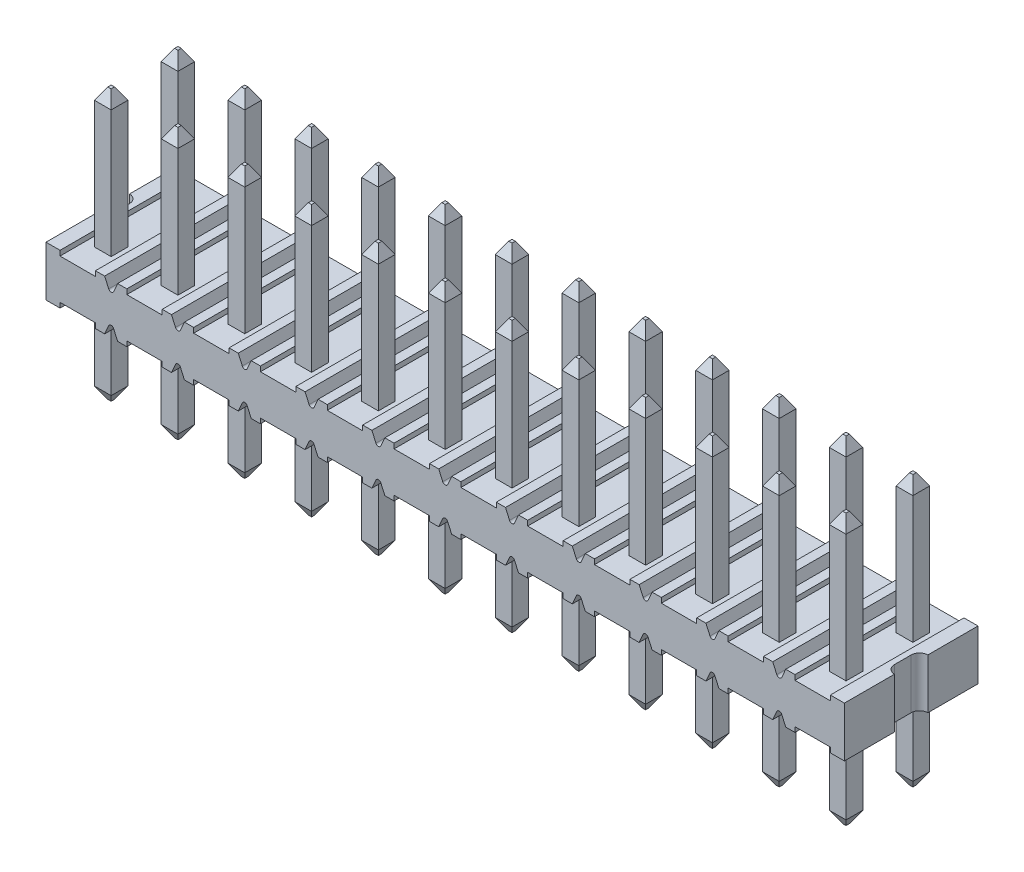
SolidWorks part; units mm, degrees
ref_plane "Front Plane" through (0, 0, 0) normal (0, 0, 1) x (1, 0, 0)
ref_plane "Top Plane" through (0, 0, 0) normal (0, 1, 0) x (1, 0, 0)
ref_plane "Right Plane" through (0, 0, 0) normal (1, 0, 0) x (0, 0, -1)
ref_plane "Plane1" through (0, -0.75, 0) normal (0, -1, 0) x (1, 0, 0)
sketch "Sketch1" plane through (0, -0.75, 0) normal (0, -1, 0) x (1, 0, 0)
  line L0 (-11.95, -2) -> (11.95, -2)
  line L1 (11.95, -2) -> (11.95, 2)
  line L2 (11.95, 2) -> (-11.95, 2)
  line L3 (-11.95, 2) -> (-11.95, -2)
extrude "Boss-Extrude1" add sketch "Sketch1" against normal blind 1.5
sketch "Sketch2" plane through (0, 0, -2) normal (0, 0, -1) x (-1, 0, 0)
  line L0 (-10.1944, 0.75) -> (-10.0731, 0.4775)
  line L1 (-9.9269, 0.4775) -> (-9.8056, 0.75)
  line L2 (-9.8056, 0.75) -> (-10.1944, 0.75)
  arc A0 (-10.0731, 0.4775) -> (-9.9269, 0.4775) centre (-10, 0.51) ccw
extrude "Cut-Extrude1" cut sketch "Sketch2" against normal through all
sketch "Sketch3" plane through (0, 0, -2) normal (0, 0, -1) x (-1, 0, 0)
  line L0 (-9.53, 0.75) -> (-9.53, 0.6)
  line L1 (-9.53, 0.6) -> (-8.47, 0.6)
  line L2 (-8.47, 0.6) -> (-8.47, 0.75)
  line L3 (-8.47, 0.75) -> (-9.53, 0.75)
extrude "Cut-Extrude2" cut sketch "Sketch3" against normal blind 4
sketch "Sketch4" plane through (0, 0, -2) normal (0, 0, -1) x (-1, 0, 0)
  line L0 (-8.1944, 0.75) -> (-8.0731, 0.4775)
  line L1 (-7.9269, 0.4775) -> (-7.8056, 0.75)
  line L2 (-7.8056, 0.75) -> (-8.1944, 0.75)
  arc A0 (-8.0731, 0.4775) -> (-7.9269, 0.4775) centre (-8, 0.51) ccw
extrude "Cut-Extrude3" cut sketch "Sketch4" against normal blind 4
sketch "Sketch5" plane through (0, 0, -2) normal (0, 0, -1) x (-1, 0, 0)
  line L0 (-7.53, 0.75) -> (-7.53, 0.6)
  line L1 (-7.53, 0.6) -> (-6.47, 0.6)
  line L2 (-6.47, 0.6) -> (-6.47, 0.75)
  line L3 (-6.47, 0.75) -> (-7.53, 0.75)
extrude "Cut-Extrude4" cut sketch "Sketch5" against normal blind 4
sketch "Sketch6" plane through (0, 0, -2) normal (0, 0, -1) x (-1, 0, 0)
  line L0 (-6.1944, 0.75) -> (-6.0731, 0.4775)
  line L1 (-5.9269, 0.4775) -> (-5.8056, 0.75)
  line L2 (-5.8056, 0.75) -> (-6.1944, 0.75)
  arc A0 (-6.0731, 0.4775) -> (-5.9269, 0.4775) centre (-6, 0.51) ccw
extrude "Cut-Extrude5" cut sketch "Sketch6" against normal blind 4
sketch "Sketch7" plane through (0, 0, -2) normal (0, 0, -1) x (-1, 0, 0)
  line L0 (-5.53, 0.75) -> (-5.53, 0.6)
  line L1 (-5.53, 0.6) -> (-4.47, 0.6)
  line L2 (-4.47, 0.6) -> (-4.47, 0.75)
  line L3 (-4.47, 0.75) -> (-5.53, 0.75)
extrude "Cut-Extrude6" cut sketch "Sketch7" against normal blind 4
sketch "Sketch8" plane through (0, 0, -2) normal (0, 0, -1) x (-1, 0, 0)
  line L0 (-4.1944, 0.75) -> (-4.0731, 0.4775)
  line L1 (-3.9269, 0.4775) -> (-3.8056, 0.75)
  line L2 (-3.8056, 0.75) -> (-4.1944, 0.75)
  arc A0 (-4.0731, 0.4775) -> (-3.9269, 0.4775) centre (-4, 0.51) ccw
extrude "Cut-Extrude7" cut sketch "Sketch8" against normal blind 4
sketch "Sketch9" plane through (0, 0, -2) normal (0, 0, -1) x (-1, 0, 0)
  line L0 (-3.53, 0.75) -> (-3.53, 0.6)
  line L1 (-3.53, 0.6) -> (-2.47, 0.6)
  line L2 (-2.47, 0.6) -> (-2.47, 0.75)
  line L3 (-2.47, 0.75) -> (-3.53, 0.75)
extrude "Cut-Extrude8" cut sketch "Sketch9" against normal blind 4
sketch "Sketch10" plane through (0, 0, -2) normal (0, 0, -1) x (-1, 0, 0)
  line L0 (-2.1944, 0.75) -> (-2.0731, 0.4775)
  line L1 (-1.9269, 0.4775) -> (-1.8056, 0.75)
  line L2 (-1.8056, 0.75) -> (-2.1944, 0.75)
  arc A0 (-2.0731, 0.4775) -> (-1.9269, 0.4775) centre (-2, 0.51) ccw
extrude "Cut-Extrude9" cut sketch "Sketch10" against normal blind 4
sketch "Sketch11" plane through (0, 0, -2) normal (0, 0, -1) x (-1, 0, 0)
  line L0 (-1.53, 0.75) -> (-1.53, 0.6)
  line L1 (-1.53, 0.6) -> (-0.47, 0.6)
  line L2 (-0.47, 0.6) -> (-0.47, 0.75)
  line L3 (-0.47, 0.75) -> (-1.53, 0.75)
extrude "Cut-Extrude10" cut sketch "Sketch11" against normal blind 4
sketch "Sketch12" plane through (0, 0, -2) normal (0, 0, -1) x (-1, 0, 0)
  line L0 (-0.1944, 0.75) -> (-0.0731, 0.4775)
  line L1 (0.0731, 0.4775) -> (0.1944, 0.75)
  line L2 (0.1944, 0.75) -> (-0.1944, 0.75)
  arc A0 (-0.0731, 0.4775) -> (0.0731, 0.4775) centre (0, 0.51) ccw
extrude "Cut-Extrude11" cut sketch "Sketch12" against normal blind 4
sketch "Sketch13" plane through (0, 0, -2) normal (0, 0, -1) x (-1, 0, 0)
  line L0 (0.47, 0.75) -> (0.47, 0.6)
  line L1 (0.47, 0.6) -> (1.53, 0.6)
  line L2 (1.53, 0.6) -> (1.53, 0.75)
  line L3 (1.53, 0.75) -> (0.47, 0.75)
extrude "Cut-Extrude12" cut sketch "Sketch13" against normal blind 4
sketch "Sketch14" plane through (0, 0, -2) normal (0, 0, -1) x (-1, 0, 0)
  line L0 (1.8056, 0.75) -> (1.9269, 0.4775)
  line L1 (2.0731, 0.4775) -> (2.1944, 0.75)
  line L2 (2.1944, 0.75) -> (1.8056, 0.75)
  arc A0 (1.9269, 0.4775) -> (2.0731, 0.4775) centre (2, 0.51) ccw
extrude "Cut-Extrude13" cut sketch "Sketch14" against normal blind 4
sketch "Sketch15" plane through (0, 0, -2) normal (0, 0, -1) x (-1, 0, 0)
  line L0 (2.47, 0.75) -> (2.47, 0.6)
  line L1 (2.47, 0.6) -> (3.53, 0.6)
  line L2 (3.53, 0.6) -> (3.53, 0.75)
  line L3 (3.53, 0.75) -> (2.47, 0.75)
extrude "Cut-Extrude14" cut sketch "Sketch15" against normal blind 4
sketch "Sketch16" plane through (0, 0, -2) normal (0, 0, -1) x (-1, 0, 0)
  line L0 (3.8056, 0.75) -> (3.9269, 0.4775)
  line L1 (4.0731, 0.4775) -> (4.1944, 0.75)
  line L2 (4.1944, 0.75) -> (3.8056, 0.75)
  arc A0 (3.9269, 0.4775) -> (4.0731, 0.4775) centre (4, 0.51) ccw
extrude "Cut-Extrude15" cut sketch "Sketch16" against normal blind 4
sketch "Sketch17" plane through (0, 0, -2) normal (0, 0, -1) x (-1, 0, 0)
  line L0 (4.47, 0.75) -> (4.47, 0.6)
  line L1 (4.47, 0.6) -> (5.53, 0.6)
  line L2 (5.53, 0.6) -> (5.53, 0.75)
  line L3 (5.53, 0.75) -> (4.47, 0.75)
extrude "Cut-Extrude16" cut sketch "Sketch17" against normal blind 4
sketch "Sketch18" plane through (0, 0, -2) normal (0, 0, -1) x (-1, 0, 0)
  line L0 (5.8056, 0.75) -> (5.9269, 0.4775)
  line L1 (6.0731, 0.4775) -> (6.1944, 0.75)
  line L2 (6.1944, 0.75) -> (5.8056, 0.75)
  arc A0 (5.9269, 0.4775) -> (6.0731, 0.4775) centre (6, 0.51) ccw
extrude "Cut-Extrude17" cut sketch "Sketch18" against normal blind 4
sketch "Sketch19" plane through (0, 0, -2) normal (0, 0, -1) x (-1, 0, 0)
  line L0 (6.47, 0.75) -> (6.47, 0.6)
  line L1 (6.47, 0.6) -> (7.53, 0.6)
  line L2 (7.53, 0.6) -> (7.53, 0.75)
  line L3 (7.53, 0.75) -> (6.47, 0.75)
extrude "Cut-Extrude18" cut sketch "Sketch19" against normal blind 4
sketch "Sketch20" plane through (0, 0, -2) normal (0, 0, -1) x (-1, 0, 0)
  line L0 (7.8056, 0.75) -> (7.9269, 0.4775)
  line L1 (8.0731, 0.4775) -> (8.1944, 0.75)
  line L2 (8.1944, 0.75) -> (7.8056, 0.75)
  arc A0 (7.9269, 0.4775) -> (8.0731, 0.4775) centre (8, 0.51) ccw
extrude "Cut-Extrude19" cut sketch "Sketch20" against normal blind 4
sketch "Sketch21" plane through (0, 0, -2) normal (0, 0, -1) x (-1, 0, 0)
  line L0 (8.47, 0.75) -> (8.47, 0.6)
  line L1 (8.47, 0.6) -> (9.53, 0.6)
  line L2 (9.53, 0.6) -> (9.53, 0.75)
  line L3 (9.53, 0.75) -> (8.47, 0.75)
extrude "Cut-Extrude20" cut sketch "Sketch21" against normal blind 4
sketch "Sketch22" plane through (0, 0, -2) normal (0, 0, -1) x (-1, 0, 0)
  line L0 (9.8056, 0.75) -> (9.9269, 0.4775)
  line L1 (10.0731, 0.4775) -> (10.1944, 0.75)
  line L2 (10.1944, 0.75) -> (9.8056, 0.75)
  arc A0 (9.9269, 0.4775) -> (10.0731, 0.4775) centre (10, 0.51) ccw
extrude "Cut-Extrude21" cut sketch "Sketch22" against normal blind 4
sketch "Sketch23" plane through (0, 0, -2) normal (0, 0, -1) x (-1, 0, 0)
  line L0 (10.47, 0.75) -> (10.47, 0.6)
  line L1 (10.47, 0.6) -> (11.53, 0.6)
  line L2 (11.53, 0.6) -> (11.53, 0.75)
  line L3 (11.53, 0.75) -> (10.47, 0.75)
extrude "Cut-Extrude22" cut sketch "Sketch23" against normal blind 4
sketch "Sketch24" plane through (0, 0, -2) normal (0, 0, -1) x (-1, 0, 0)
  line L0 (11.53, -0.75) -> (11.53, -0.6)
  line L1 (11.53, -0.6) -> (10.47, -0.6)
  line L2 (10.47, -0.6) -> (10.47, -0.75)
  line L3 (10.47, -0.75) -> (11.53, -0.75)
extrude "Cut-Extrude23" cut sketch "Sketch24" against normal through all
sketch "Sketch25" plane through (0, 0, -2) normal (0, 0, -1) x (-1, 0, 0)
  line L0 (10.1944, -0.75) -> (10.0731, -0.4775)
  line L1 (9.9269, -0.4775) -> (9.8056, -0.75)
  line L2 (9.8056, -0.75) -> (10.1944, -0.75)
  arc A0 (10.0731, -0.4775) -> (9.9269, -0.4775) centre (10, -0.51) ccw
extrude "Cut-Extrude24" cut sketch "Sketch25" against normal blind 4
sketch "Sketch26" plane through (0, 0, -2) normal (0, 0, -1) x (-1, 0, 0)
  line L0 (9.53, -0.75) -> (9.53, -0.6)
  line L1 (9.53, -0.6) -> (8.47, -0.6)
  line L2 (8.47, -0.6) -> (8.47, -0.75)
  line L3 (8.47, -0.75) -> (9.53, -0.75)
extrude "Cut-Extrude25" cut sketch "Sketch26" against normal blind 4
sketch "Sketch27" plane through (0, 0, -2) normal (0, 0, -1) x (-1, 0, 0)
  line L0 (8.1944, -0.75) -> (8.0731, -0.4775)
  line L1 (7.9269, -0.4775) -> (7.8056, -0.75)
  line L2 (7.8056, -0.75) -> (8.1944, -0.75)
  arc A0 (8.0731, -0.4775) -> (7.9269, -0.4775) centre (8, -0.51) ccw
extrude "Cut-Extrude26" cut sketch "Sketch27" against normal blind 4
sketch "Sketch28" plane through (0, 0, -2) normal (0, 0, -1) x (-1, 0, 0)
  line L0 (7.53, -0.75) -> (7.53, -0.6)
  line L1 (7.53, -0.6) -> (6.47, -0.6)
  line L2 (6.47, -0.6) -> (6.47, -0.75)
  line L3 (6.47, -0.75) -> (7.53, -0.75)
extrude "Cut-Extrude27" cut sketch "Sketch28" against normal blind 4
sketch "Sketch29" plane through (0, 0, -2) normal (0, 0, -1) x (-1, 0, 0)
  line L0 (6.1944, -0.75) -> (6.0731, -0.4775)
  line L1 (5.9269, -0.4775) -> (5.8056, -0.75)
  line L2 (5.8056, -0.75) -> (6.1944, -0.75)
  arc A0 (6.0731, -0.4775) -> (5.9269, -0.4775) centre (6, -0.51) ccw
extrude "Cut-Extrude28" cut sketch "Sketch29" against normal blind 4
sketch "Sketch30" plane through (0, 0, -2) normal (0, 0, -1) x (-1, 0, 0)
  line L0 (5.53, -0.75) -> (5.53, -0.6)
  line L1 (5.53, -0.6) -> (4.47, -0.6)
  line L2 (4.47, -0.6) -> (4.47, -0.75)
  line L3 (4.47, -0.75) -> (5.53, -0.75)
extrude "Cut-Extrude29" cut sketch "Sketch30" against normal blind 4
sketch "Sketch31" plane through (0, 0, -2) normal (0, 0, -1) x (-1, 0, 0)
  line L0 (4.1944, -0.75) -> (4.0731, -0.4775)
  line L1 (3.9269, -0.4775) -> (3.8056, -0.75)
  line L2 (3.8056, -0.75) -> (4.1944, -0.75)
  arc A0 (4.0731, -0.4775) -> (3.9269, -0.4775) centre (4, -0.51) ccw
extrude "Cut-Extrude30" cut sketch "Sketch31" against normal blind 4
sketch "Sketch32" plane through (0, 0, -2) normal (0, 0, -1) x (-1, 0, 0)
  line L0 (3.53, -0.75) -> (3.53, -0.6)
  line L1 (3.53, -0.6) -> (2.47, -0.6)
  line L2 (2.47, -0.6) -> (2.47, -0.75)
  line L3 (2.47, -0.75) -> (3.53, -0.75)
extrude "Cut-Extrude31" cut sketch "Sketch32" against normal blind 4
sketch "Sketch33" plane through (0, 0, -2) normal (0, 0, -1) x (-1, 0, 0)
  line L0 (2.1944, -0.75) -> (2.0731, -0.4775)
  line L1 (1.9269, -0.4775) -> (1.8056, -0.75)
  line L2 (1.8056, -0.75) -> (2.1944, -0.75)
  arc A0 (2.0731, -0.4775) -> (1.9269, -0.4775) centre (2, -0.51) ccw
extrude "Cut-Extrude32" cut sketch "Sketch33" against normal blind 4
sketch "Sketch34" plane through (0, 0, -2) normal (0, 0, -1) x (-1, 0, 0)
  line L0 (1.53, -0.75) -> (1.53, -0.6)
  line L1 (1.53, -0.6) -> (0.47, -0.6)
  line L2 (0.47, -0.6) -> (0.47, -0.75)
  line L3 (0.47, -0.75) -> (1.53, -0.75)
extrude "Cut-Extrude33" cut sketch "Sketch34" against normal blind 4
sketch "Sketch35" plane through (0, 0, -2) normal (0, 0, -1) x (-1, 0, 0)
  line L0 (0.1944, -0.75) -> (0.0731, -0.4775)
  line L1 (-0.0731, -0.4775) -> (-0.1944, -0.75)
  line L2 (-0.1944, -0.75) -> (0.1944, -0.75)
  arc A0 (0.0731, -0.4775) -> (-0.0731, -0.4775) centre (0, -0.51) ccw
extrude "Cut-Extrude34" cut sketch "Sketch35" against normal blind 4
sketch "Sketch36" plane through (0, 0, -2) normal (0, 0, -1) x (-1, 0, 0)
  line L0 (-0.47, -0.75) -> (-0.47, -0.6)
  line L1 (-0.47, -0.6) -> (-1.53, -0.6)
  line L2 (-1.53, -0.6) -> (-1.53, -0.75)
  line L3 (-1.53, -0.75) -> (-0.47, -0.75)
extrude "Cut-Extrude35" cut sketch "Sketch36" against normal blind 4
sketch "Sketch37" plane through (0, 0, -2) normal (0, 0, -1) x (-1, 0, 0)
  line L0 (-1.8056, -0.75) -> (-1.9269, -0.4775)
  line L1 (-2.0731, -0.4775) -> (-2.1944, -0.75)
  line L2 (-2.1944, -0.75) -> (-1.8056, -0.75)
  arc A0 (-1.9269, -0.4775) -> (-2.0731, -0.4775) centre (-2, -0.51) ccw
extrude "Cut-Extrude36" cut sketch "Sketch37" against normal blind 4
sketch "Sketch38" plane through (0, 0, -2) normal (0, 0, -1) x (-1, 0, 0)
  line L0 (-2.47, -0.75) -> (-2.47, -0.6)
  line L1 (-2.47, -0.6) -> (-3.53, -0.6)
  line L2 (-3.53, -0.6) -> (-3.53, -0.75)
  line L3 (-3.53, -0.75) -> (-2.47, -0.75)
extrude "Cut-Extrude37" cut sketch "Sketch38" against normal blind 4
sketch "Sketch39" plane through (0, 0, -2) normal (0, 0, -1) x (-1, 0, 0)
  line L0 (-3.8056, -0.75) -> (-3.9269, -0.4775)
  line L1 (-4.0731, -0.4775) -> (-4.1944, -0.75)
  line L2 (-4.1944, -0.75) -> (-3.8056, -0.75)
  arc A0 (-3.9269, -0.4775) -> (-4.0731, -0.4775) centre (-4, -0.51) ccw
extrude "Cut-Extrude38" cut sketch "Sketch39" against normal blind 4
sketch "Sketch40" plane through (0, 0, -2) normal (0, 0, -1) x (-1, 0, 0)
  line L0 (-4.47, -0.75) -> (-4.47, -0.6)
  line L1 (-4.47, -0.6) -> (-5.53, -0.6)
  line L2 (-5.53, -0.6) -> (-5.53, -0.75)
  line L3 (-5.53, -0.75) -> (-4.47, -0.75)
extrude "Cut-Extrude39" cut sketch "Sketch40" against normal blind 4
sketch "Sketch41" plane through (0, 0, -2) normal (0, 0, -1) x (-1, 0, 0)
  line L0 (-5.8056, -0.75) -> (-5.9269, -0.4775)
  line L1 (-6.0731, -0.4775) -> (-6.1944, -0.75)
  line L2 (-6.1944, -0.75) -> (-5.8056, -0.75)
  arc A0 (-5.9269, -0.4775) -> (-6.0731, -0.4775) centre (-6, -0.51) ccw
extrude "Cut-Extrude40" cut sketch "Sketch41" against normal blind 4
sketch "Sketch42" plane through (0, 0, -2) normal (0, 0, -1) x (-1, 0, 0)
  line L0 (-6.47, -0.75) -> (-6.47, -0.6)
  line L1 (-6.47, -0.6) -> (-7.53, -0.6)
  line L2 (-7.53, -0.6) -> (-7.53, -0.75)
  line L3 (-7.53, -0.75) -> (-6.47, -0.75)
extrude "Cut-Extrude41" cut sketch "Sketch42" against normal blind 4
sketch "Sketch43" plane through (0, 0, -2) normal (0, 0, -1) x (-1, 0, 0)
  line L0 (-7.8056, -0.75) -> (-7.9269, -0.4775)
  line L1 (-8.0731, -0.4775) -> (-8.1944, -0.75)
  line L2 (-8.1944, -0.75) -> (-7.8056, -0.75)
  arc A0 (-7.9269, -0.4775) -> (-8.0731, -0.4775) centre (-8, -0.51) ccw
extrude "Cut-Extrude42" cut sketch "Sketch43" against normal blind 4
sketch "Sketch44" plane through (0, 0, -2) normal (0, 0, -1) x (-1, 0, 0)
  line L0 (-8.47, -0.75) -> (-8.47, -0.6)
  line L1 (-8.47, -0.6) -> (-9.53, -0.6)
  line L2 (-9.53, -0.6) -> (-9.53, -0.75)
  line L3 (-9.53, -0.75) -> (-8.47, -0.75)
extrude "Cut-Extrude43" cut sketch "Sketch44" against normal blind 4
sketch "Sketch45" plane through (0, 0, -2) normal (0, 0, -1) x (-1, 0, 0)
  line L0 (-9.8056, -0.75) -> (-9.9269, -0.4775)
  line L1 (-10.0731, -0.4775) -> (-10.1944, -0.75)
  line L2 (-10.1944, -0.75) -> (-9.8056, -0.75)
  arc A0 (-9.9269, -0.4775) -> (-10.0731, -0.4775) centre (-10, -0.51) ccw
extrude "Cut-Extrude44" cut sketch "Sketch45" against normal blind 4
sketch "Sketch46" plane through (0, 0, -2) normal (0, 0, -1) x (-1, 0, 0)
  line L0 (-10.47, -0.75) -> (-10.47, -0.6)
  line L1 (-10.47, -0.6) -> (-11.53, -0.6)
  line L2 (-11.53, -0.6) -> (-11.53, -0.75)
  line L3 (-11.53, -0.75) -> (-10.47, -0.75)
extrude "Cut-Extrude45" cut sketch "Sketch46" against normal blind 4
sketch "Sketch47" plane through (0, 0.75, 0) normal (0, 1, 0) x (-1, 0, 0)
  line L0 (-11.95, 0.5) -> (-11.95, -0.5)
  line L1 (-11.7, -0.25) -> (-11.7, 0.25)
  arc A0 (-11.95, -0.5) -> (-11.7, -0.25) centre (-11.95, -0.25) ccw
  arc A1 (-11.7, 0.25) -> (-11.95, 0.5) centre (-11.95, 0.25) ccw
extrude "Cut-Extrude46" cut sketch "Sketch47" against normal through all
sketch "Sketch48" plane through (0, 0.75, 0) normal (0, 1, 0) x (-1, 0, 0)
  line L0 (11.95, -0.5) -> (11.95, 0.5)
  line L1 (11.7, 0.25) -> (11.7, -0.25)
  arc A0 (11.95, 0.5) -> (11.7, 0.25) centre (11.95, 0.25) ccw
  arc A1 (11.7, -0.25) -> (11.95, -0.5) centre (11.95, -0.25) ccw
extrude "Cut-Extrude47" cut sketch "Sketch48" against normal blind 1.5
sketch "Sketch49" plane through (0, 0, -2) normal (0, 0, -1) x (-1, 0, 0)
  line L0 (-11.53, 0.75) -> (-11.53, 0.6)
  line L1 (-11.53, 0.6) -> (-10.47, 0.6)
  line L2 (-10.47, 0.6) -> (-10.47, 0.75)
  line L3 (-10.47, 0.75) -> (-11.53, 0.75)
extrude "Cut-Extrude48" cut sketch "Sketch49" against normal through all
sketch "Sketch50" plane through (0, -0.6, 0) normal (0, -1, 0) x (1, 0, 0)
  line L0 (10.75, -1.25) -> (10.75, -0.75)
  line L1 (10.75, -0.75) -> (11.25, -0.75)
  line L2 (11.25, -0.75) -> (11.25, -1.25)
  line L3 (11.25, -1.25) -> (10.75, -1.25)
extrude "Boss-Extrude2" add sketch "Sketch50" along normal blind 2.75
sketch "Sketch51" plane through (0, -0.6, 0) normal (0, -1, 0) x (1, 0, 0)
  line L0 (10.75, 1.25) -> (11.25, 1.25)
  line L1 (11.25, 1.25) -> (11.25, 0.75)
  line L2 (11.25, 0.75) -> (10.75, 0.75)
  line L3 (10.75, 0.75) -> (10.75, 1.25)
extrude "Boss-Extrude3" add sketch "Sketch51" along normal blind 2.75
sketch "Sketch52" plane through (0, -0.6, 0) normal (0, -1, 0) x (1, 0, 0)
  line L0 (9.25, -0.75) -> (9.25, -1.25)
  line L1 (9.25, -1.25) -> (8.75, -1.25)
  line L2 (8.75, -1.25) -> (8.75, -0.75)
  line L3 (8.75, -0.75) -> (9.25, -0.75)
extrude "Boss-Extrude4" add sketch "Sketch52" along normal blind 2.75
sketch "Sketch53" plane through (0, -0.6, 0) normal (0, -1, 0) x (1, 0, 0)
  line L0 (9.25, 1.25) -> (9.25, 0.75)
  line L1 (9.25, 0.75) -> (8.75, 0.75)
  line L2 (8.75, 0.75) -> (8.75, 1.25)
  line L3 (8.75, 1.25) -> (9.25, 1.25)
extrude "Boss-Extrude5" add sketch "Sketch53" along normal blind 2.75
sketch "Sketch54" plane through (0, -0.6, 0) normal (0, -1, 0) x (1, 0, 0)
  line L0 (7.25, -0.75) -> (7.25, -1.25)
  line L1 (7.25, -1.25) -> (6.75, -1.25)
  line L2 (6.75, -1.25) -> (6.75, -0.75)
  line L3 (6.75, -0.75) -> (7.25, -0.75)
extrude "Boss-Extrude6" add sketch "Sketch54" along normal blind 2.75
sketch "Sketch55" plane through (0, -0.6, 0) normal (0, -1, 0) x (1, 0, 0)
  line L0 (7.25, 1.25) -> (7.25, 0.75)
  line L1 (7.25, 0.75) -> (6.75, 0.75)
  line L2 (6.75, 0.75) -> (6.75, 1.25)
  line L3 (6.75, 1.25) -> (7.25, 1.25)
extrude "Boss-Extrude7" add sketch "Sketch55" along normal blind 2.75
sketch "Sketch56" plane through (0, -0.6, 0) normal (0, -1, 0) x (1, 0, 0)
  line L0 (5.25, -0.75) -> (5.25, -1.25)
  line L1 (5.25, -1.25) -> (4.75, -1.25)
  line L2 (4.75, -1.25) -> (4.75, -0.75)
  line L3 (4.75, -0.75) -> (5.25, -0.75)
extrude "Boss-Extrude8" add sketch "Sketch56" along normal blind 2.75
sketch "Sketch57" plane through (0, -0.6, 0) normal (0, -1, 0) x (1, 0, 0)
  line L0 (5.25, 1.25) -> (5.25, 0.75)
  line L1 (5.25, 0.75) -> (4.75, 0.75)
  line L2 (4.75, 0.75) -> (4.75, 1.25)
  line L3 (4.75, 1.25) -> (5.25, 1.25)
extrude "Boss-Extrude9" add sketch "Sketch57" along normal blind 2.75
sketch "Sketch58" plane through (0, -0.6, 0) normal (0, -1, 0) x (1, 0, 0)
  line L0 (3.25, -0.75) -> (3.25, -1.25)
  line L1 (3.25, -1.25) -> (2.75, -1.25)
  line L2 (2.75, -1.25) -> (2.75, -0.75)
  line L3 (2.75, -0.75) -> (3.25, -0.75)
extrude "Boss-Extrude10" add sketch "Sketch58" along normal blind 2.75
sketch "Sketch59" plane through (0, -0.6, 0) normal (0, -1, 0) x (1, 0, 0)
  line L0 (3.25, 1.25) -> (3.25, 0.75)
  line L1 (3.25, 0.75) -> (2.75, 0.75)
  line L2 (2.75, 0.75) -> (2.75, 1.25)
  line L3 (2.75, 1.25) -> (3.25, 1.25)
extrude "Boss-Extrude11" add sketch "Sketch59" along normal blind 2.75
sketch "Sketch60" plane through (0, -0.6, 0) normal (0, -1, 0) x (1, 0, 0)
  line L0 (1.25, -0.75) -> (1.25, -1.25)
  line L1 (1.25, -1.25) -> (0.75, -1.25)
  line L2 (0.75, -1.25) -> (0.75, -0.75)
  line L3 (0.75, -0.75) -> (1.25, -0.75)
extrude "Boss-Extrude12" add sketch "Sketch60" along normal blind 2.75
sketch "Sketch61" plane through (0, -0.6, 0) normal (0, -1, 0) x (1, 0, 0)
  line L0 (1.25, 1.25) -> (1.25, 0.75)
  line L1 (1.25, 0.75) -> (0.75, 0.75)
  line L2 (0.75, 0.75) -> (0.75, 1.25)
  line L3 (0.75, 1.25) -> (1.25, 1.25)
extrude "Boss-Extrude13" add sketch "Sketch61" along normal blind 2.75
sketch "Sketch62" plane through (0, -0.6, 0) normal (0, -1, 0) x (1, 0, 0)
  line L0 (-0.75, -0.75) -> (-0.75, -1.25)
  line L1 (-0.75, -1.25) -> (-1.25, -1.25)
  line L2 (-1.25, -1.25) -> (-1.25, -0.75)
  line L3 (-1.25, -0.75) -> (-0.75, -0.75)
extrude "Boss-Extrude14" add sketch "Sketch62" along normal blind 2.75
sketch "Sketch63" plane through (0, -0.6, 0) normal (0, -1, 0) x (1, 0, 0)
  line L0 (-0.75, 1.25) -> (-0.75, 0.75)
  line L1 (-0.75, 0.75) -> (-1.25, 0.75)
  line L2 (-1.25, 0.75) -> (-1.25, 1.25)
  line L3 (-1.25, 1.25) -> (-0.75, 1.25)
extrude "Boss-Extrude15" add sketch "Sketch63" along normal blind 2.75
sketch "Sketch64" plane through (0, -0.6, 0) normal (0, -1, 0) x (1, 0, 0)
  line L0 (-2.75, -0.75) -> (-2.75, -1.25)
  line L1 (-2.75, -1.25) -> (-3.25, -1.25)
  line L2 (-3.25, -1.25) -> (-3.25, -0.75)
  line L3 (-3.25, -0.75) -> (-2.75, -0.75)
extrude "Boss-Extrude16" add sketch "Sketch64" along normal blind 2.75
sketch "Sketch65" plane through (0, -0.6, 0) normal (0, -1, 0) x (1, 0, 0)
  line L0 (-2.75, 1.25) -> (-2.75, 0.75)
  line L1 (-2.75, 0.75) -> (-3.25, 0.75)
  line L2 (-3.25, 0.75) -> (-3.25, 1.25)
  line L3 (-3.25, 1.25) -> (-2.75, 1.25)
extrude "Boss-Extrude17" add sketch "Sketch65" along normal blind 2.75
sketch "Sketch66" plane through (0, -0.6, 0) normal (0, -1, 0) x (1, 0, 0)
  line L0 (-4.75, -0.75) -> (-4.75, -1.25)
  line L1 (-4.75, -1.25) -> (-5.25, -1.25)
  line L2 (-5.25, -1.25) -> (-5.25, -0.75)
  line L3 (-5.25, -0.75) -> (-4.75, -0.75)
extrude "Boss-Extrude18" add sketch "Sketch66" along normal blind 2.75
sketch "Sketch67" plane through (0, -0.6, 0) normal (0, -1, 0) x (1, 0, 0)
  line L0 (-4.75, 1.25) -> (-4.75, 0.75)
  line L1 (-4.75, 0.75) -> (-5.25, 0.75)
  line L2 (-5.25, 0.75) -> (-5.25, 1.25)
  line L3 (-5.25, 1.25) -> (-4.75, 1.25)
extrude "Boss-Extrude19" add sketch "Sketch67" along normal blind 2.75
sketch "Sketch68" plane through (0, -0.6, 0) normal (0, -1, 0) x (1, 0, 0)
  line L0 (-6.75, -0.75) -> (-6.75, -1.25)
  line L1 (-6.75, -1.25) -> (-7.25, -1.25)
  line L2 (-7.25, -1.25) -> (-7.25, -0.75)
  line L3 (-7.25, -0.75) -> (-6.75, -0.75)
extrude "Boss-Extrude20" add sketch "Sketch68" along normal blind 2.75
sketch "Sketch69" plane through (0, -0.6, 0) normal (0, -1, 0) x (1, 0, 0)
  line L0 (-6.75, 1.25) -> (-6.75, 0.75)
  line L1 (-6.75, 0.75) -> (-7.25, 0.75)
  line L2 (-7.25, 0.75) -> (-7.25, 1.25)
  line L3 (-7.25, 1.25) -> (-6.75, 1.25)
extrude "Boss-Extrude21" add sketch "Sketch69" along normal blind 2.75
sketch "Sketch70" plane through (0, -0.6, 0) normal (0, -1, 0) x (1, 0, 0)
  line L0 (-8.75, -0.75) -> (-8.75, -1.25)
  line L1 (-8.75, -1.25) -> (-9.25, -1.25)
  line L2 (-9.25, -1.25) -> (-9.25, -0.75)
  line L3 (-9.25, -0.75) -> (-8.75, -0.75)
extrude "Boss-Extrude22" add sketch "Sketch70" along normal blind 2.75
sketch "Sketch71" plane through (0, -0.6, 0) normal (0, -1, 0) x (1, 0, 0)
  line L0 (-8.75, 1.25) -> (-8.75, 0.75)
  line L1 (-8.75, 0.75) -> (-9.25, 0.75)
  line L2 (-9.25, 0.75) -> (-9.25, 1.25)
  line L3 (-9.25, 1.25) -> (-8.75, 1.25)
extrude "Boss-Extrude23" add sketch "Sketch71" along normal blind 2.75
sketch "Sketch72" plane through (0, -0.6, 0) normal (0, -1, 0) x (1, 0, 0)
  line L0 (-10.75, -0.75) -> (-10.75, -1.25)
  line L1 (-10.75, -1.25) -> (-11.25, -1.25)
  line L2 (-11.25, -1.25) -> (-11.25, -0.75)
  line L3 (-11.25, -0.75) -> (-10.75, -0.75)
extrude "Boss-Extrude24" add sketch "Sketch72" along normal blind 2.75
sketch "Sketch73" plane through (0, -0.6, 0) normal (0, -1, 0) x (1, 0, 0)
  line L0 (-10.75, 1.25) -> (-10.75, 0.75)
  line L1 (-10.75, 0.75) -> (-11.25, 0.75)
  line L2 (-11.25, 0.75) -> (-11.25, 1.25)
  line L3 (-11.25, 1.25) -> (-10.75, 1.25)
extrude "Boss-Extrude25" add sketch "Sketch73" along normal blind 2.75
sketch "Sketch74" plane through (0, 0.6, 0) normal (0, 1, 0) x (-1, 0, 0)
  line L0 (11.25, -1.25) -> (10.75, -1.25)
  line L1 (10.75, -1.25) -> (10.75, -0.75)
  line L2 (10.75, -0.75) -> (11.25, -0.75)
  line L3 (11.25, -0.75) -> (11.25, -1.25)
extrude "Boss-Extrude26" add sketch "Sketch74" along normal blind 4.15
sketch "Sketch75" plane through (0, 0.6, 0) normal (0, 1, 0) x (-1, 0, 0)
  line L0 (11.25, 1.25) -> (11.25, 0.75)
  line L1 (11.25, 0.75) -> (10.75, 0.75)
  line L2 (10.75, 0.75) -> (10.75, 1.25)
  line L3 (10.75, 1.25) -> (11.25, 1.25)
extrude "Boss-Extrude27" add sketch "Sketch75" along normal blind 4.15
sketch "Sketch76" plane through (0, 0.6, 0) normal (0, 1, 0) x (-1, 0, 0)
  line L0 (9.25, -1.25) -> (8.75, -1.25)
  line L1 (8.75, -1.25) -> (8.75, -0.75)
  line L2 (8.75, -0.75) -> (9.25, -0.75)
  line L3 (9.25, -0.75) -> (9.25, -1.25)
extrude "Boss-Extrude28" add sketch "Sketch76" along normal blind 4.15
sketch "Sketch77" plane through (0, 0.6, 0) normal (0, 1, 0) x (-1, 0, 0)
  line L0 (9.25, 1.25) -> (9.25, 0.75)
  line L1 (9.25, 0.75) -> (8.75, 0.75)
  line L2 (8.75, 0.75) -> (8.75, 1.25)
  line L3 (8.75, 1.25) -> (9.25, 1.25)
extrude "Boss-Extrude29" add sketch "Sketch77" along normal blind 4.15
sketch "Sketch78" plane through (0, 0.6, 0) normal (0, 1, 0) x (-1, 0, 0)
  line L0 (7.25, -1.25) -> (6.75, -1.25)
  line L1 (6.75, -1.25) -> (6.75, -0.75)
  line L2 (6.75, -0.75) -> (7.25, -0.75)
  line L3 (7.25, -0.75) -> (7.25, -1.25)
extrude "Boss-Extrude30" add sketch "Sketch78" along normal blind 4.15
sketch "Sketch79" plane through (0, 0.6, 0) normal (0, 1, 0) x (-1, 0, 0)
  line L0 (7.25, 1.25) -> (7.25, 0.75)
  line L1 (7.25, 0.75) -> (6.75, 0.75)
  line L2 (6.75, 0.75) -> (6.75, 1.25)
  line L3 (6.75, 1.25) -> (7.25, 1.25)
extrude "Boss-Extrude31" add sketch "Sketch79" along normal blind 4.15
sketch "Sketch80" plane through (0, 0.6, 0) normal (0, 1, 0) x (-1, 0, 0)
  line L0 (5.25, -1.25) -> (4.75, -1.25)
  line L1 (4.75, -1.25) -> (4.75, -0.75)
  line L2 (4.75, -0.75) -> (5.25, -0.75)
  line L3 (5.25, -0.75) -> (5.25, -1.25)
extrude "Boss-Extrude32" add sketch "Sketch80" along normal blind 4.15
sketch "Sketch81" plane through (0, 0.6, 0) normal (0, 1, 0) x (-1, 0, 0)
  line L0 (5.25, 1.25) -> (5.25, 0.75)
  line L1 (5.25, 0.75) -> (4.75, 0.75)
  line L2 (4.75, 0.75) -> (4.75, 1.25)
  line L3 (4.75, 1.25) -> (5.25, 1.25)
extrude "Boss-Extrude33" add sketch "Sketch81" along normal blind 4.15
sketch "Sketch82" plane through (0, 0.6, 0) normal (0, 1, 0) x (-1, 0, 0)
  line L0 (3.25, -1.25) -> (2.75, -1.25)
  line L1 (2.75, -1.25) -> (2.75, -0.75)
  line L2 (2.75, -0.75) -> (3.25, -0.75)
  line L3 (3.25, -0.75) -> (3.25, -1.25)
extrude "Boss-Extrude34" add sketch "Sketch82" along normal blind 4.15
sketch "Sketch83" plane through (0, 0.6, 0) normal (0, 1, 0) x (-1, 0, 0)
  line L0 (3.25, 1.25) -> (3.25, 0.75)
  line L1 (3.25, 0.75) -> (2.75, 0.75)
  line L2 (2.75, 0.75) -> (2.75, 1.25)
  line L3 (2.75, 1.25) -> (3.25, 1.25)
extrude "Boss-Extrude35" add sketch "Sketch83" along normal blind 4.15
sketch "Sketch84" plane through (0, 0.6, 0) normal (0, 1, 0) x (-1, 0, 0)
  line L0 (1.25, -1.25) -> (0.75, -1.25)
  line L1 (0.75, -1.25) -> (0.75, -0.75)
  line L2 (0.75, -0.75) -> (1.25, -0.75)
  line L3 (1.25, -0.75) -> (1.25, -1.25)
extrude "Boss-Extrude36" add sketch "Sketch84" along normal blind 4.15
sketch "Sketch85" plane through (0, 0.6, 0) normal (0, 1, 0) x (-1, 0, 0)
  line L0 (1.25, 1.25) -> (1.25, 0.75)
  line L1 (1.25, 0.75) -> (0.75, 0.75)
  line L2 (0.75, 0.75) -> (0.75, 1.25)
  line L3 (0.75, 1.25) -> (1.25, 1.25)
extrude "Boss-Extrude37" add sketch "Sketch85" along normal blind 4.15
sketch "Sketch86" plane through (0, 0.6, 0) normal (0, 1, 0) x (-1, 0, 0)
  line L0 (-0.75, -1.25) -> (-1.25, -1.25)
  line L1 (-1.25, -1.25) -> (-1.25, -0.75)
  line L2 (-1.25, -0.75) -> (-0.75, -0.75)
  line L3 (-0.75, -0.75) -> (-0.75, -1.25)
extrude "Boss-Extrude38" add sketch "Sketch86" along normal blind 4.15
sketch "Sketch87" plane through (0, 0.6, 0) normal (0, 1, 0) x (-1, 0, 0)
  line L0 (-0.75, 1.25) -> (-0.75, 0.75)
  line L1 (-0.75, 0.75) -> (-1.25, 0.75)
  line L2 (-1.25, 0.75) -> (-1.25, 1.25)
  line L3 (-1.25, 1.25) -> (-0.75, 1.25)
extrude "Boss-Extrude39" add sketch "Sketch87" along normal blind 4.15
sketch "Sketch88" plane through (0, 0.6, 0) normal (0, 1, 0) x (-1, 0, 0)
  line L0 (-2.75, -1.25) -> (-3.25, -1.25)
  line L1 (-3.25, -1.25) -> (-3.25, -0.75)
  line L2 (-3.25, -0.75) -> (-2.75, -0.75)
  line L3 (-2.75, -0.75) -> (-2.75, -1.25)
extrude "Boss-Extrude40" add sketch "Sketch88" along normal blind 4.15
sketch "Sketch89" plane through (0, 0.6, 0) normal (0, 1, 0) x (-1, 0, 0)
  line L0 (-2.75, 1.25) -> (-2.75, 0.75)
  line L1 (-2.75, 0.75) -> (-3.25, 0.75)
  line L2 (-3.25, 0.75) -> (-3.25, 1.25)
  line L3 (-3.25, 1.25) -> (-2.75, 1.25)
extrude "Boss-Extrude41" add sketch "Sketch89" along normal blind 4.15
sketch "Sketch90" plane through (0, 0.6, 0) normal (0, 1, 0) x (-1, 0, 0)
  line L0 (-4.75, -1.25) -> (-5.25, -1.25)
  line L1 (-5.25, -1.25) -> (-5.25, -0.75)
  line L2 (-5.25, -0.75) -> (-4.75, -0.75)
  line L3 (-4.75, -0.75) -> (-4.75, -1.25)
extrude "Boss-Extrude42" add sketch "Sketch90" along normal blind 4.15
sketch "Sketch91" plane through (0, 0.6, 0) normal (0, 1, 0) x (-1, 0, 0)
  line L0 (-4.75, 1.25) -> (-4.75, 0.75)
  line L1 (-4.75, 0.75) -> (-5.25, 0.75)
  line L2 (-5.25, 0.75) -> (-5.25, 1.25)
  line L3 (-5.25, 1.25) -> (-4.75, 1.25)
extrude "Boss-Extrude43" add sketch "Sketch91" along normal blind 4.15
sketch "Sketch92" plane through (0, 0.6, 0) normal (0, 1, 0) x (-1, 0, 0)
  line L0 (-6.75, -1.25) -> (-7.25, -1.25)
  line L1 (-7.25, -1.25) -> (-7.25, -0.75)
  line L2 (-7.25, -0.75) -> (-6.75, -0.75)
  line L3 (-6.75, -0.75) -> (-6.75, -1.25)
extrude "Boss-Extrude44" add sketch "Sketch92" along normal blind 4.15
sketch "Sketch93" plane through (0, 0.6, 0) normal (0, 1, 0) x (-1, 0, 0)
  line L0 (-6.75, 1.25) -> (-6.75, 0.75)
  line L1 (-6.75, 0.75) -> (-7.25, 0.75)
  line L2 (-7.25, 0.75) -> (-7.25, 1.25)
  line L3 (-7.25, 1.25) -> (-6.75, 1.25)
extrude "Boss-Extrude45" add sketch "Sketch93" along normal blind 4.15
sketch "Sketch94" plane through (0, 0.6, 0) normal (0, 1, 0) x (-1, 0, 0)
  line L0 (-8.75, -1.25) -> (-9.25, -1.25)
  line L1 (-9.25, -1.25) -> (-9.25, -0.75)
  line L2 (-9.25, -0.75) -> (-8.75, -0.75)
  line L3 (-8.75, -0.75) -> (-8.75, -1.25)
extrude "Boss-Extrude46" add sketch "Sketch94" along normal blind 4.15
sketch "Sketch95" plane through (0, 0.6, 0) normal (0, 1, 0) x (-1, 0, 0)
  line L0 (-8.75, 1.25) -> (-8.75, 0.75)
  line L1 (-8.75, 0.75) -> (-9.25, 0.75)
  line L2 (-9.25, 0.75) -> (-9.25, 1.25)
  line L3 (-9.25, 1.25) -> (-8.75, 1.25)
extrude "Boss-Extrude47" add sketch "Sketch95" along normal blind 4.15
sketch "Sketch96" plane through (0, 0.6, 0) normal (0, 1, 0) x (-1, 0, 0)
  line L0 (-10.75, -1.25) -> (-11.25, -1.25)
  line L1 (-11.25, -1.25) -> (-11.25, -0.75)
  line L2 (-11.25, -0.75) -> (-10.75, -0.75)
  line L3 (-10.75, -0.75) -> (-10.75, -1.25)
extrude "Boss-Extrude48" add sketch "Sketch96" along normal blind 4.15
sketch "Sketch97" plane through (0, 0.6, 0) normal (0, 1, 0) x (-1, 0, 0)
  line L0 (-10.75, 1.25) -> (-10.75, 0.75)
  line L1 (-10.75, 0.75) -> (-11.25, 0.75)
  line L2 (-11.25, 0.75) -> (-11.25, 1.25)
  line L3 (-11.25, 1.25) -> (-10.75, 1.25)
extrude "Boss-Extrude49" add sketch "Sketch97" along normal blind 4.15
chamfer "Chamfer1" distance 0.2 angle 60 192 edges at (-2.75, 4.75, -1) (-3, 4.75, -0.75) (-3, 4.75, -1.25) (-3.25, 4.75, -1) (-10.75, 4.75, -1) (-11, 4.75, -0.75) (-11, 4.75, -1.25) (-11.25, 4.75, -1) (5.25, 4.75, -1) (5, 4.75, -0.75) (5, 4.75, -1.25) (4.75, 4.75, -1) (11.25, -3.35, 1) (11, -3.35, 0.75) (11, -3.35, 1.25) (10.75, -3.35, 1) (-6.75, 4.75, -1) (-7, 4.75, -0.75) (-7, 4.75, -1.25) (-7.25, 4.75, -1) (11, -3.35, -0.75) (11.25, -3.35, -1) (10.75, -3.35, -1) (11, -3.35, -1.25) (1.25, 4.75, -1) (1, 4.75, -0.75) (1, 4.75, -1.25) (0.75, 4.75, -1) (9.25, 4.75, -1) (9, 4.75, -0.75) (9, 4.75, -1.25) (8.75, 4.75, -1) (9, -3.35, -1.25) (9.25, -3.35, -1) (8.75, -3.35, -1) (9, -3.35, -0.75) (-8.75, 4.75, -1) (-9, 4.75, -0.75) (-9, 4.75, -1.25) (-9.25, 4.75, -1) (9, -3.35, 0.75) (9.25, -3.35, 1) (8.75, -3.35, 1) (9, -3.35, 1.25) (-4.75, 4.75, -1) (-5, 4.75, -0.75) (-5, 4.75, -1.25) (-5.25, 4.75, -1) (-0.75, 4.75, -1) (-1, 4.75, -0.75) (-1, 4.75, -1.25) (-1.25, 4.75, -1) (3.25, 4.75, -1) (3, 4.75, -0.75) (3, 4.75, -1.25) (2.75, 4.75, -1) (7.25, 4.75, -1) (7, 4.75, -0.75) (7, 4.75, -1.25) (6.75, 4.75, -1) (11.25, 4.75, -1) (11, 4.75, -0.75) (11, 4.75, -1.25) (10.75, 4.75, -1) (-11, 4.75, 0.75) (-10.75, 4.75, 1) (-11.25, 4.75, 1) (-11, 4.75, 1.25) (-9, 4.75, 0.75) (-8.75, 4.75, 1) (-9.25, 4.75, 1) (-9, 4.75, 1.25) (7, -3.35, -1.25) (7.25, -3.35, -1) (6.75, -3.35, -1) (7, -3.35, -0.75) (-7, 4.75, 0.75) (-6.75, 4.75, 1) (-7.25, 4.75, 1) (-7, 4.75, 1.25) (7, -3.35, 0.75) (7.25, -3.35, 1) (6.75, -3.35, 1) (7, -3.35, 1.25) (-5, 4.75, 0.75) (-4.75, 4.75, 1) (-5.25, 4.75, 1) (-5, 4.75, 1.25) (-3, 4.75, 0.75) (-2.75, 4.75, 1) (-3.25, 4.75, 1) (-3, 4.75, 1.25) (-1, 4.75, 0.75) (-0.75, 4.75, 1) (-1.25, 4.75, 1) (-1, 4.75, 1.25) (1, 4.75, 0.75) (1.25, 4.75, 1) (0.75, 4.75, 1) (1, 4.75, 1.25) (3, 4.75, 0.75) (3.25, 4.75, 1) (2.75, 4.75, 1) (3, 4.75, 1.25) (5, 4.75, 0.75) (5.25, 4.75, 1) (4.75, 4.75, 1) (5, 4.75, 1.25) (7, 4.75, 0.75) (7.25, 4.75, 1) (6.75, 4.75, 1) (7, 4.75, 1.25) (5, -3.35, -1.25) (5.25, -3.35, -1) (4.75, -3.35, -1) (5, -3.35, -0.75) (9, 4.75, 0.75) (9.25, 4.75, 1) (8.75, 4.75, 1) (9, 4.75, 1.25) (5, -3.35, 0.75) (5.25, -3.35, 1) (4.75, -3.35, 1) (5, -3.35, 1.25) (11, 4.75, 0.75) (11.25, 4.75, 1) (10.75, 4.75, 1) (11, 4.75, 1.25) (3, -3.35, -1.25) (3.25, -3.35, -1) (2.75, -3.35, -1) (3, -3.35, -0.75) (3, -3.35, 0.75) (3.25, -3.35, 1) (2.75, -3.35, 1) (3, -3.35, 1.25) (1, -3.35, -1.25) (1.25, -3.35, -1) (0.75, -3.35, -1) (1, -3.35, -0.75) (1, -3.35, 0.75) (1.25, -3.35, 1) (0.75, -3.35, 1) (1, -3.35, 1.25) (-1, -3.35, -1.25) (-0.75, -3.35, -1) (-1.25, -3.35, -1) (-1, -3.35, -0.75) (-1, -3.35, 0.75) (-0.75, -3.35, 1) (-1.25, -3.35, 1) (-1, -3.35, 1.25) (-3, -3.35, -1.25) (-2.75, -3.35, -1) (-3.25, -3.35, -1) (-3, -3.35, -0.75) (-3, -3.35, 0.75) (-2.75, -3.35, 1) (-3.25, -3.35, 1) (-3, -3.35, 1.25) (-5, -3.35, -1.25) (-4.75, -3.35, -1) (-5.25, -3.35, -1) (-5, -3.35, -0.75) (-5, -3.35, 0.75) (-4.75, -3.35, 1) (-5.25, -3.35, 1) (-5, -3.35, 1.25) (-7, -3.35, -1.25) (-6.75, -3.35, -1) (-7.25, -3.35, -1) (-7, -3.35, -0.75) (-7, -3.35, 0.75) (-6.75, -3.35, 1) (-7.25, -3.35, 1) (-7, -3.35, 1.25) (-9, -3.35, -1.25) (-8.75, -3.35, -1) (-9.25, -3.35, -1) (-9, -3.35, -0.75) (-9, -3.35, 0.75) (-8.75, -3.35, 1) (-9.25, -3.35, 1) (-9, -3.35, 1.25) (-11, -3.35, -1.25) (-10.75, -3.35, -1) (-11.25, -3.35, -1) (-11, -3.35, -0.75) (-11, -3.35, 0.75) (-10.75, -3.35, 1) (-11.25, -3.35, 1) (-11, -3.35, 1.25)
